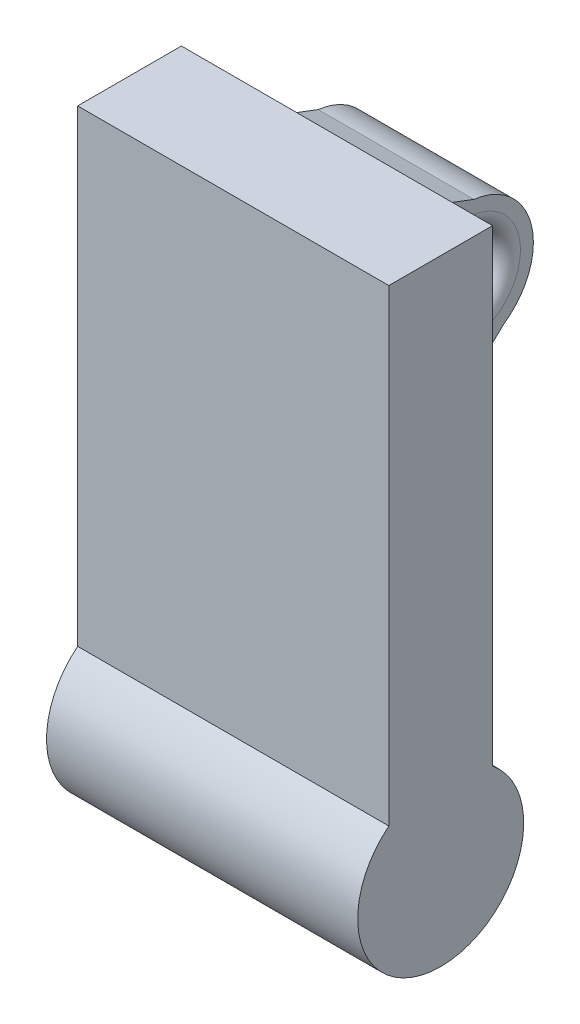
SolidWorks part; units mm, degrees
ref_plane "Front Plane" through (0, 0, 0) normal (0, 0, 1) x (1, 0, 0)
ref_plane "Top Plane" through (0, 0, 0) normal (0, 1, 0) x (1, 0, 0)
ref_plane "Right Plane" through (0, 0, 0) normal (1, 0, 0) x (0, 0, -1)
sketch "Sketch2" plane through (0, 0, 0) normal (1, 0, 0) x (0, 0, -1)
  circle A0 centre (0, 0) radius 16
extrude "Boss-Extrude1" add sketch "Sketch2" along normal blind 60 contours A0
sketch "Sketch3" plane through (0, 0, 0) normal (1, 0, 0) x (0, 0, -1)
  circle A0 centre (0, 0) radius 3.75
extrude "Cut-Extrude1" cut sketch "Sketch3" along normal blind 8.5
sketch "Sketch4" plane through (0, 0, 0) normal (1, 0, 0) x (0, 0, -1)
  line L0 (4.9329, 12.49) -> (10, 12.49)
  line L1 (10, 12.49) -> (-10, 12.49)
  line L2 (-10, 12.49) -> (-10, 15.8222)
  line L5 (10, 12.49) -> (10, 22.7394)
  line L6 (10, 22.7394) -> (-10, 22.7394)
  line L7 (-10, 22.7394) -> (-10, 15.8222)
  circle A0 centre (0, 0) radius 16 construction
extrude "Boss-Extrude3" add sketch "Sketch4" along normal through all contours L5 L6 L7 L2 L1
sketch "Sketch5" plane through (0, 0, 0) normal (1, 0, 0) x (0, 0, -1)
  line L0 (10, 22.7394) -> (10, 102.7394)
  line L2 (-10, 22.7394) -> (-10, 102.7394)
  line L3 (-10, 102.7394) -> (10, 102.7394)
  line L4 (10, 22.7394) -> (-10, 22.7394)
  dimension "D1" = 80
extrude "Boss-Extrude4" add sketch "Sketch5" along normal blind 60
ref_plane "Plane1" through (30, 0, 0) normal (1, 0, 0) x (0, 0, -1)
sketch "Sketch8" plane through (30, 0, 0) normal (1, 0, 0) x (0, 0, -1)
  circle A0 centre (19.8694, 81.0137) radius 7.5
  circle A1 centre (19.8694, 81.0137) radius 13
extrude "Boss-Extrude5" add sketch "Sketch8" along normal blind 15 and the other way blind 15
sketch "Sketch9" plane through (30, 0, 0) normal (1, 0, 0) x (0, 0, -1)
  line L29 (10, 53.862) -> (30.2106, 73.1358)
  line L30 (10, 12.49) -> (10, 102.7394) construction
  line L31 (30.2106, 73.1358) -> (27.5485, 88.9988)
  line L32 (27.5485, 88.9988) -> (27.5485, 75.9273)
  line L33 (27.5485, 75.9273) -> (23.4279, 71.9976)
  line L34 (23.4279, 71.9976) -> (12.9082, 73.9624)
  line L35 (12.9082, 73.9624) -> (11.7158, 81.0673)
  line L36 (11.7158, 81.0673) -> (12.8618, 87.2025)
  line L37 (12.8618, 87.2025) -> (20.1053, 90.4629)
  line L38 (20.1053, 90.4629) -> (21.4167, 93.9213)
  line L39 (21.4167, 93.9213) -> (10, 98.2506)
  line L40 (10, 98.2506) -> (4.6568, 69.6434)
  line L41 (4.6568, 69.6434) -> (10, 53.862)
  arc A3 (10, 72.5523) -> (10, 89.475) centre (19.8694, 81.0137) ccw construction
extrude "Boss-Extrude6" add sketch "Sketch9" along normal blind 15 and the other way blind 15
fillet "Fillet5" radius 3 2 edges at (15, 81.0137, -27.3694) (45, 81.0137, -27.3694)
